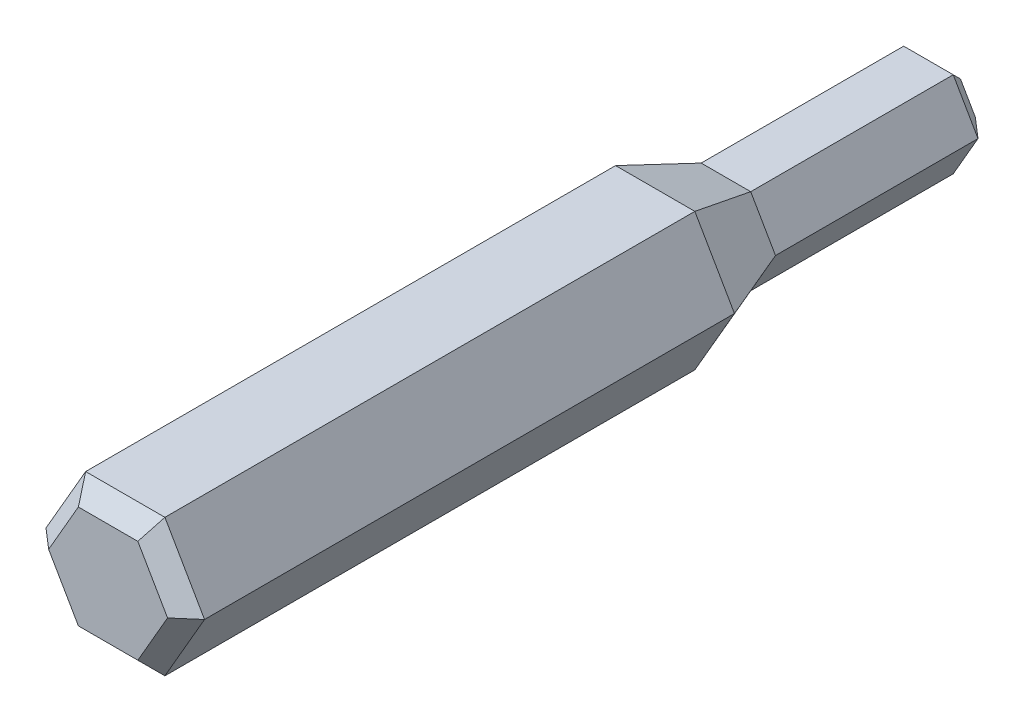
SolidWorks part; units mm, degrees
ref_plane "前视基准面" through (0, 0, 0) normal (0, 0, 1) x (1, 0, 0)
ref_plane "上视基准面" through (0, 0, 0) normal (0, 1, 0) x (1, 0, 0)
ref_plane "右视基准面" through (0, 0, 0) normal (1, 0, 0) x (0, 0, -1)
sketch "草图1" plane through (0, 0, 0) normal (0, 0, 1) x (1, 0, 0)
  line L1 (2.3094, 0) -> (1.1547, 2)
  line L2 (1.1547, 2) -> (-1.1547, 2)
  line L3 (-1.1547, 2) -> (-2.3094, 0)
  line L4 (-2.3094, 0) -> (-1.1547, -2)
  line L5 (-1.1547, -2) -> (1.1547, -2)
  line L6 (1.1547, -2) -> (2.3094, 0)
  circle A0 centre (0, 0) radius 2 construction
  dimension "D1" = 4
extrude "凸台-拉伸1" add sketch "草图1" along normal blind 18
chamfer "倒角1" distance 0.5 angle 45 6 edges at (0, -2, 18) (-1.7321, -1, 18) (-1.7321, 1, 18) (0, 2, 18) (1.7321, 1, 18) (1.7321, -1, 18)
sketch "草图2" plane through (0, 0, 0) normal (0, 0, -1) x (-1, 0, 0)
  line L1 (1.4434, 0) -> (0.7217, 1.25)
  line L2 (0.7217, 1.25) -> (-0.7217, 1.25)
  line L3 (-0.7217, 1.25) -> (-1.4434, 0)
  line L4 (-1.4434, 0) -> (-0.7217, -1.25)
  line L5 (-0.7217, -1.25) -> (0.7217, -1.25)
  line L6 (0.7217, -1.25) -> (1.4434, 0)
  circle A0 centre (0, 0) radius 1.25 construction
  dimension "D1" = 2.5
extrude "凸台-拉伸2" add sketch "草图2" along normal blind 6.4
chamfer "倒角3" distance 0.75 angle 70 6 edges at (-1.7321, 1, 0) (-1.7321, -1, 0) (0, -2, 0) (1.7321, -1, 0) (1.7321, 1, 0) (0, 2, 0) first distance on face at (0, 0, 0)
chamfer "倒角4" distance 0.5 angle 45 6 edges at (0, -1.25, -6.4) (1.0825, -0.625, -6.4) (1.0825, 0.625, -6.4) (0, 1.25, -6.4) (-1.0825, 0.625, -6.4) (-1.0825, -0.625, -6.4)
